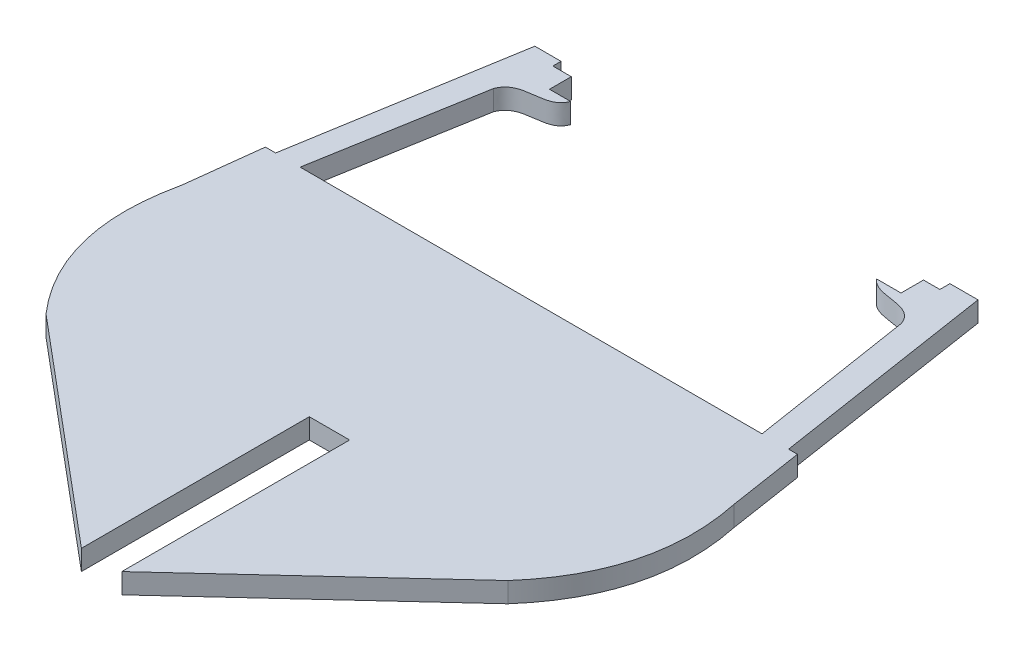
SolidWorks part; units mm, degrees
ref_plane "前视基准面" through (0, 0, 0) normal (0, 0, 1) x (1, 0, 0)
ref_plane "上视基准面" through (0, 0, 0) normal (0, 1, 0) x (1, 0, 0)
ref_plane "右视基准面" through (0, 0, 0) normal (1, 0, 0) x (0, 0, -1)
sketch "草图1" plane through (0, 0, 0) normal (0, 1, 0) x (1, 0, 0)
  line L0 (100.9517, -14.8657) -> (98.6543, 0)
  line L1 (98.6543, 0) -> (96.8974, 0)
  line L2 (96.8974, 0) -> (90.0302, 44.4352)
  line L3 (90.0302, 44.4352) -> (84.4643, 44.4352)
  line L4 (84.4643, 44.4352) -> (84.4643, 42.4349)
  line L5 (84.4643, 42.4349) -> (81.2209, 42.4349)
  line L6 (81.2209, 42.4349) -> (81.2209, 37.9751)
  line L7 (81.2209, 37.9751) -> (76.3557, 37.9751)
  line L8 (86.4914, 32.7046) -> (91.6269, 0)
  line L9 (91.6269, 0) -> (0, 0)
  line L10 (0, 0) -> (5.676, 32.7046)
  line L11 (15.5414, 38.1103) -> (11.352, 38.1103)
  line L12 (11.352, 38.1103) -> (11.352, 42.4349)
  line L13 (11.352, 42.4349) -> (7.7031, 42.4349)
  line L14 (7.7031, 42.4349) -> (7.7031, 44.0566)
  line L15 (7.7031, 44.0566) -> (2.5044, 44.0566)
  line L16 (2.5044, 44.0566) -> (-4.8651, 0)
  line L17 (-4.8651, 0) -> (-6.8923, 0)
  line L18 (-6.8923, 0) -> (-8.6491, -14.8657)
  line L19 (0, -50.4083) -> (43.7863, -87.1671)
  line L20 (43.7863, -87.1671) -> (43.7863, -41.9671)
  line L21 (43.7863, -41.9671) -> (51.7863, -41.9671)
  line L22 (51.7863, -41.9671) -> (51.7863, -87.1671)
  line L23 (51.7863, -87.1671) -> (91.6269, -50.4083)
  spline S0 degree 3 poles (76.3557, 37.9751) (79.0549, 34.7141) (84.9275, 37.3973) (86.4914, 32.7046) knots 0 0 0 0 1 1 1 1
  spline S1 degree 3 poles (15.5414, 38.1103) (13.9609, 34.0013) (7.4625, 37.2422) (5.676, 32.7046) knots 0 0 0 0 1 1 1 1
  spline S2 degree 2 poles (100.9517, -14.8657) (105.1983, -35.0059) (91.6269, -50.4083) knots 0 0 0 1 1 1
  spline S3 degree 2 poles (-8.6491, -14.8657) (-13.1534, -35.2606) (0, -50.4083) knots 0 0 0 1 1 1
  dimension "D1" = 8
  dimension "D2" = 45.2
extrude "凸台-拉伸1" add sketch "草图1" along normal blind 4
